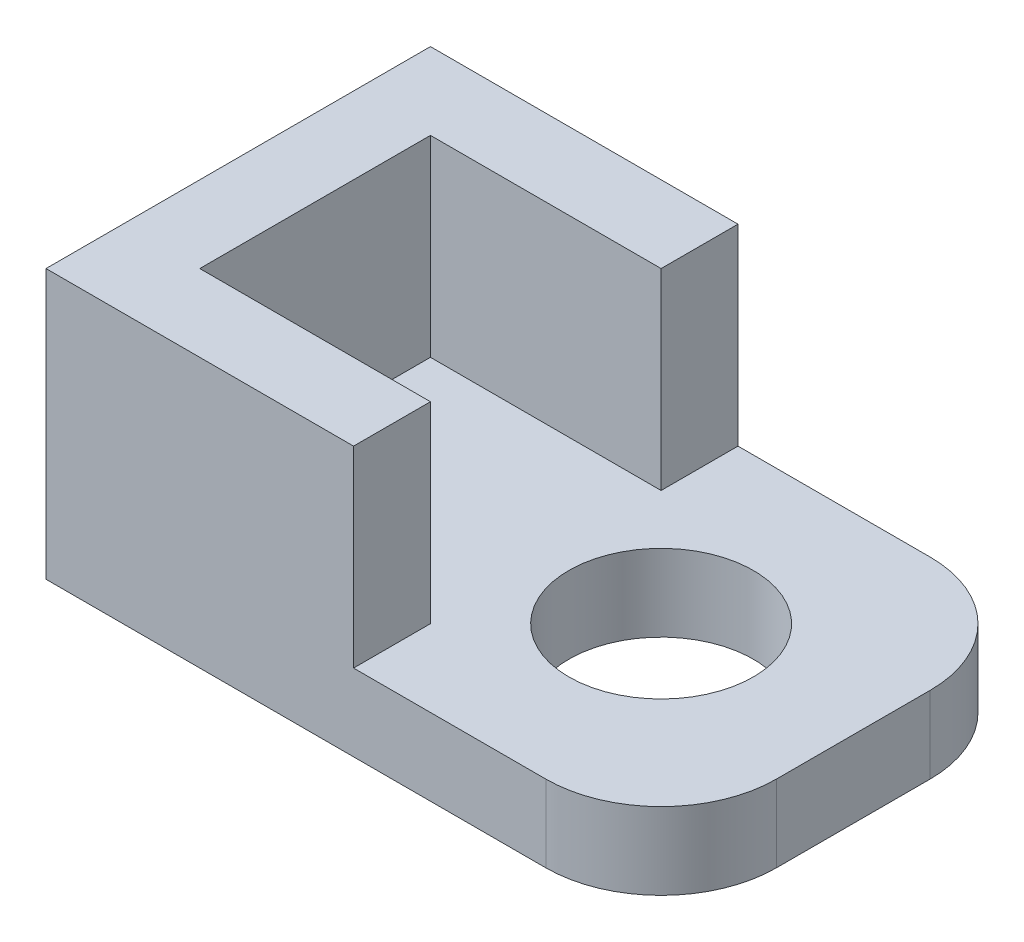
SolidWorks part; units mm, degrees
ref_plane "Front Plane" through (0, 0, 0) normal (0, 0, 1) x (1, 0, 0)
ref_plane "Top Plane" through (0, 0, 0) normal (0, 1, 0) x (1, 0, 0)
ref_plane "Right Plane" through (0, 0, 0) normal (1, 0, 0) x (0, 0, -1)
sketch "Sketch1" plane through (0, 0, 0) normal (0, 1, 0) x (1, 0, 0)
  line L0 (0, 25) -> (0, 15)
  line L1 (-40, 25) -> (40, 25)
  line L2 (-40, 25) -> (-40, -25)
  line L3 (-40, -25) -> (40, -25)
  line L4 (40, 25) -> (40, -25)
  line L5 (-40, 25) -> (40, -25) construction
  line L6 (-40, -25) -> (40, 25) construction
  line L7 (0, 15) -> (-30, 15)
  line L8 (-30, 15) -> (-30, -15)
  line L9 (-30, -15) -> (0, -15)
  line L10 (0, -15) -> (0, -25)
  circle A0 centre (15, 0) radius 12
  point P0 (0, 0)
  point P14 (0, 20)
  dimension "D1" = 80
  dimension "D7" = 24
  dimension "D8" = 25
  dimension "D9" = 25
  dimension "D2" = 50
  dimension "D3" = 40
  dimension "D4" = 40
  dimension "D5" = 30
  dimension "D6" = 10
  dimension "D10" = 10
extrude "Boss-Extrude1" add sketch "Sketch1" along normal blind 10 contours L9 L10 L3 L4 L1 L0 L7 L8 A0 region at (20, 0, -24.1398)
extrude "Boss-Extrude2" add sketch "Sketch1<3>" along normal blind 35 contours L10 L9 L8 L7 L0 L1 L2 L3 region at (-0.6403, 0, -20)
sketch "Sketch1<3>" plane through (0, 0, 0) normal (0, 1, 0) x (1, 0, 0) same geometry as "Sketch1"
fillet "Fillet1" radius 15 2 edges at (40, 5, -25) (40, 5, 25)
